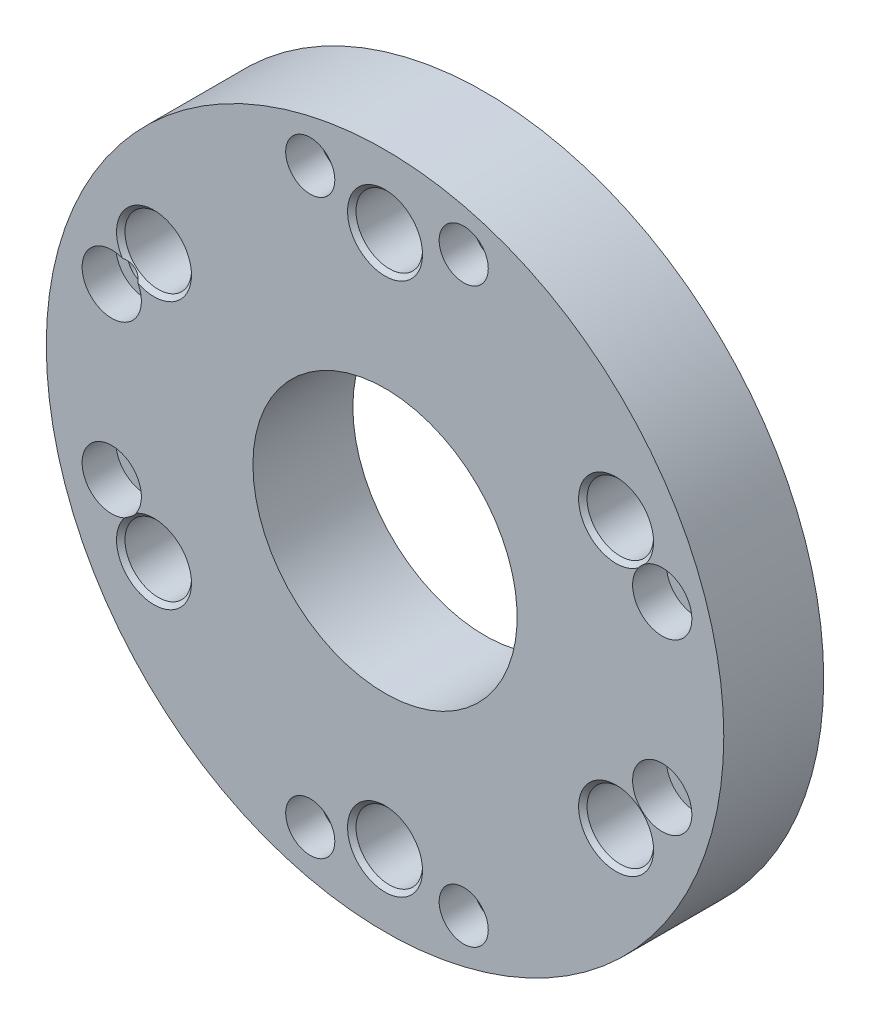
SolidWorks part; units mm, degrees
ref_plane "前视基准面" through (0, 0, 0) normal (0, 0, 1) x (1, 0, 0)
ref_plane "上视基准面" through (0, 0, 0) normal (0, 1, 0) x (1, 0, 0)
ref_plane "右视基准面" through (0, 0, 0) normal (1, 0, 0) x (0, 0, -1)
sketch "草图1" plane through (0, 0, 0) normal (0, 0, 1) x (1, 0, 0)
  circle A0 centre (0, 0) radius 40
  dimension "D1" = 80
extrude "凸台-拉伸1" add sketch "草图1" along normal blind 11.8
sketch "草图2" plane through (0, 0, 0) normal (0, 0, -1) x (-1, 0, 0)
  circle A0 centre (-32.7306, 10.1246) radius 2.15
  circle A1 centre (-32.7306, -9.8754) radius 2.15
  circle A2 centre (32.2694, -9.8754) radius 2.15
  circle A3 centre (32.2694, 10.1246) radius 2.15
  circle A4 centre (-9.2906, 33.9346) radius 1.75
  circle A5 centre (8.8294, 33.9346) radius 1.75
  circle A6 centre (8.8294, -33.6854) radius 1.75
  circle A7 centre (-9.2906, -33.6854) radius 1.75
  dimension "D1" = 4.3
  dimension "D2" = 3.5
  dimension "D3" = 3.5
  dimension "D4" = 3.5
  dimension "D5" = 3.5
  dimension "D6" = 4.3
  dimension "D7" = 4.3
  dimension "D8" = 4.3
extrude "切除-拉伸1" cut sketch "草图2" against normal through all
sketch "草图3" plane through (0, 0, 0) normal (0, 0, -1) x (-1, 0, 0)
  line L0 (0, 0) -> (0, 41.6751) construction
  circle A0 centre (0, 0) radius 31.5 construction
  circle A1 centre (0, 31.5) radius 3.925
  circle A2 centre (27.2798, 15.75) radius 3.925
  circle A3 centre (27.2798, -15.75) radius 3.925
  circle A4 centre (0, -31.5) radius 3.925
  circle A5 centre (-27.2798, -15.75) radius 3.925
  circle A6 centre (-27.2798, 15.75) radius 3.925
  circle A7 centre (0, 0) radius 15.6
  point P20 (0, 0)
  dimension "D1" = 63
  dimension "D2" = 7.85
  dimension "D4" = 31.2
  dimension "D3" = 6
extrude "切除-拉伸2" cut sketch "草图3" against normal through all
sketch "草图5" plane through (0, 0, 11.8) normal (0, 0, 1) x (1, 0, 0)
  circle A0 centre (-8.8294, -33.6854) radius 2.9
  circle A1 centre (-8.8294, 33.9346) radius 2.9
  circle A2 centre (-32.2694, 10.1246) radius 3.5
  circle A3 centre (-32.2694, -9.8754) radius 3.5
  circle A4 centre (9.2906, 33.9346) radius 2.9
  circle A5 centre (32.7306, 10.1246) radius 3.5
  circle A6 centre (32.7306, -9.8754) radius 3.5
  circle A7 centre (9.2906, -33.6854) radius 2.9
  dimension "D1" = 5.8
  dimension "D2" = 7
  dimension "D3" = 7
  dimension "D4" = 5.8
  dimension "D5" = 5.8
  dimension "D6" = 7
  dimension "D7" = 7
  dimension "D8" = 5.8
extrude "切除-拉伸4" cut sketch "草图5" against normal blind 4
chamfer "倒角1" distance 0.5 angle 45 6 edges at (-3.925, -31.5, 11.8) (-31.2048, -15.75, 11.8) (23.3548, -15.75, 11.8) (23.3548, 15.75, 11.8) (-3.925, 31.5, 11.8) (-31.2048, 15.75, 11.8)
